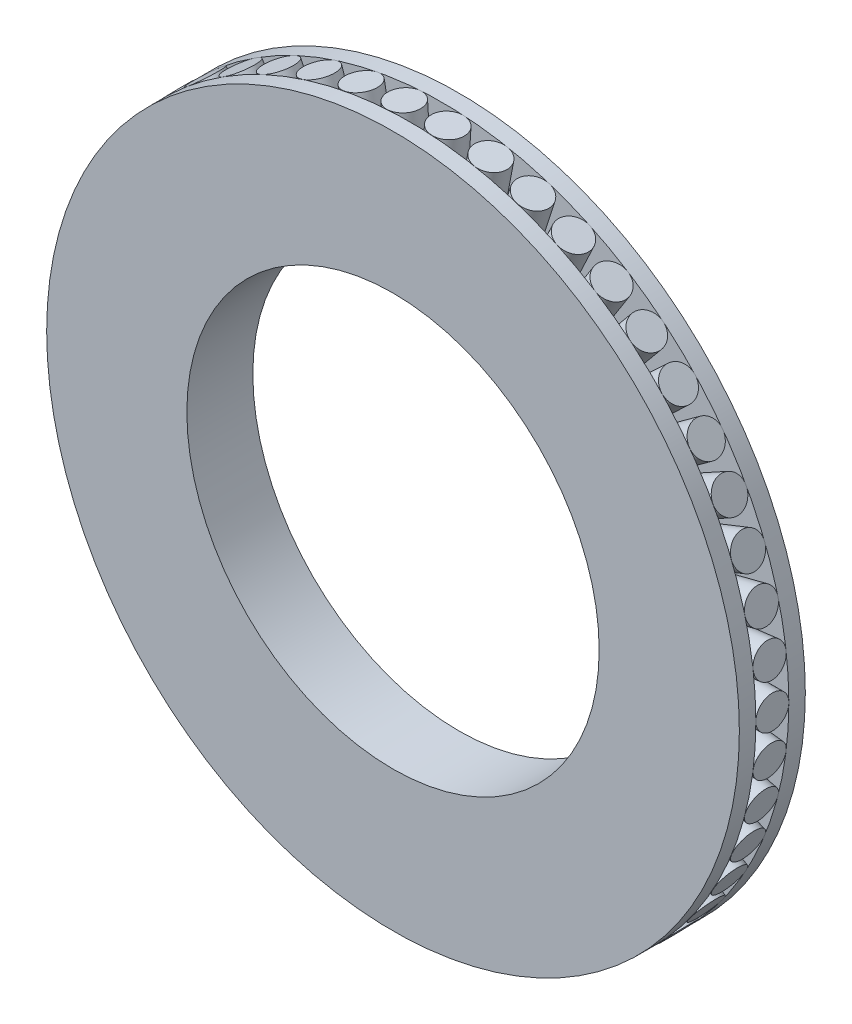
SolidWorks part; units mm, degrees
ref_plane "前视基准面" through (0, 0, 0) normal (0, 0, 1) x (1, 0, 0)
ref_plane "上视基准面" through (0, 0, 0) normal (0, 1, 0) x (1, 0, 0)
ref_plane "右视基准面" through (0, 0, 0) normal (1, 0, 0) x (0, 0, -1)
sketch "草图1" plane through (0, 0, 0) normal (0, 0, 1) x (1, 0, 0)
  circle A0 centre (0, 0) radius 12.5
  circle A1 centre (0, 0) radius 21
  dimension "D1" = 42
  dimension "D2" = 25
extrude "凸台-拉伸1" add sketch "草图1" along normal blind 4
ref_plane "基准面1" through (0, 0, 2) normal (0, 0, -1) x (-1, 0, 0)
sketch "草图2" plane through (0, 0, 2) normal (0, 0, -1) x (-1, 0, 0)
  circle A0 centre (0, 0) radius 21
  circle A1 centre (0, 0) radius 15
extrude "切除-拉伸1" cut sketch "草图2" against normal blind 1 and the other way blind 1
ref_plane "基准面2" through (17, 0, 0) normal (1, 0, 0) x (0, 0, -1)
sketch "草图3" plane through (17, 0, 0) normal (1, 0, 0) x (0, 0, -1)
  line L0 (-2, -23.1) -> (-2, 23.1) construction
  circle A0 centre (-2, 0) radius 1
extrude "凸台-拉伸2" add sketch "草图3" along normal blind 4 and the other way blind 1 separate body
ref_axis "基准轴1" through (0, 0, 4) along (0, 0, -1)
pattern_circular "阵列(圆周)1" count 50 over 360 about axis through (0, 0, 4) along (0, 0, -1) of bodies 108
